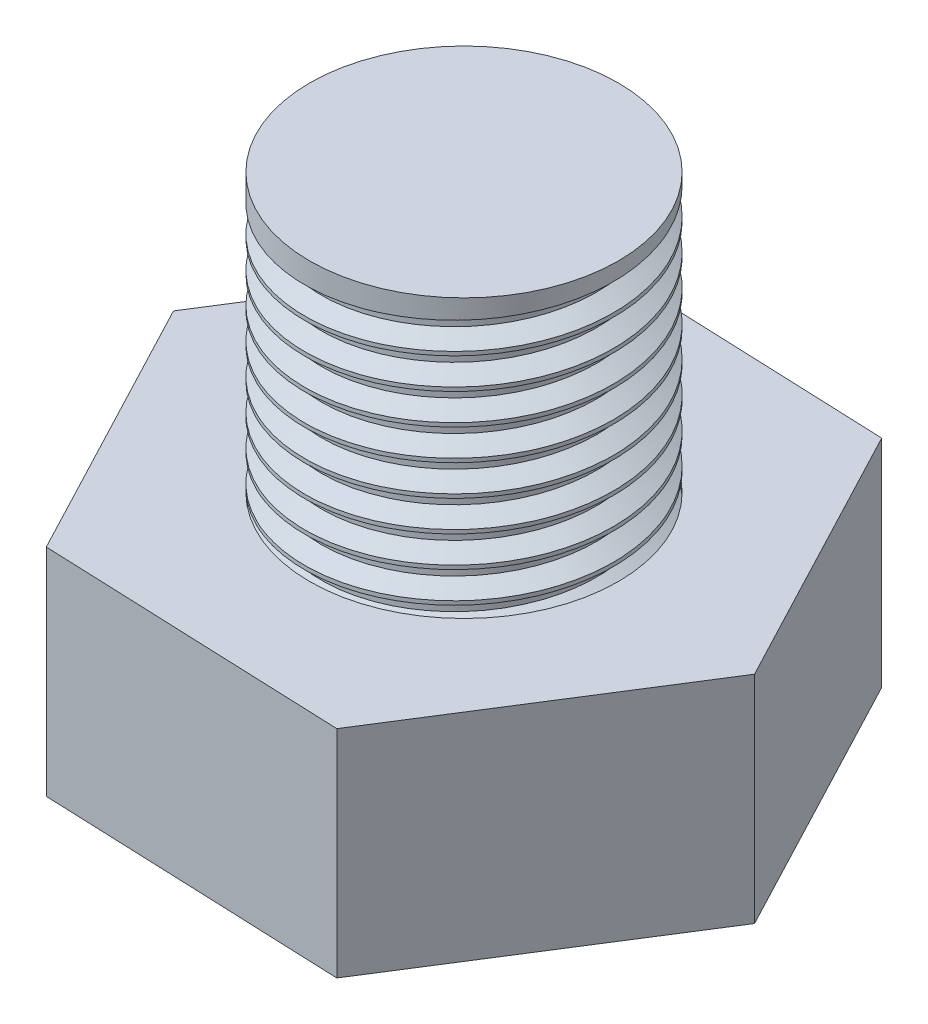
SolidWorks part; units mm, degrees
ref_plane "Front Plane" through (0, 0, 0) normal (0, 0, 1) x (1, 0, 0)
ref_plane "Top Plane" through (0, 0, 0) normal (0, 1, 0) x (1, 0, 0)
ref_plane "Right Plane" through (0, 0, 0) normal (1, 0, 0) x (0, 0, -1)
sketch "Sketch1" plane through (0, 0, 0) normal (0, 1, 0) x (1, 0, 0)
  line L1 (4.5661, -8.6882) -> (9.8072, -0.3898)
  line L2 (9.8072, -0.3898) -> (5.2412, 8.2984)
  line L3 (5.2412, 8.2984) -> (-4.5661, 8.6882)
  line L4 (-4.5661, 8.6882) -> (-9.8072, 0.3898)
  line L5 (-9.8072, 0.3898) -> (-5.2412, -8.2984)
  line L6 (-5.2412, -8.2984) -> (4.5661, -8.6882)
  circle A0 centre (0, 0) radius 8.5 construction
  dimension "D1" = 17
extrude "Boss-Extrude1" add sketch "Sketch1" along normal blind 7
sketch "Sketch2" plane through (0, 7, 0) normal (0, 1, 0) x (1, 0, 0)
  circle A0 centre (0, 0) radius 5
  dimension "D1" = 10
extrude "Boss-Extrude2" add sketch "Sketch2" along normal blind 9
thread "Thread1" pitch 1 method cut profile "Thread Profile1" start angle 0, offset 0, length 10, pitch 1, diameter 10
ref_plane "Plane1" through (-5, 16, 0) normal (0, 0, 1) x (-1, 0, 0)
sketch "Thread Profile1" plane through (-5, 16, 0) normal (0, 0, 1) x (-1, 0, 0)
  line L0 (0, 0) -> (0, 1) construction
  line L11 (0, 0) -> (0, 0.875)
  line L12 (0, 0.875) -> (-0.5413, 0.5625)
  line L13 (-0.5413, 0.5625) -> (-0.5413, 0.3125)
  line L15 (-0.5413, 0.3125) -> (0, 0)
  line L17 (-0.5413, 0.4375) -> (0, 0.4375) construction
  point P2 (0, 0)
  dimension "Pitch" = 1
  dimension "Profile_Angle" = 60
  dimension "Profile_Land" = 0.25
  dimension "Profile_Height" = 0.5413
